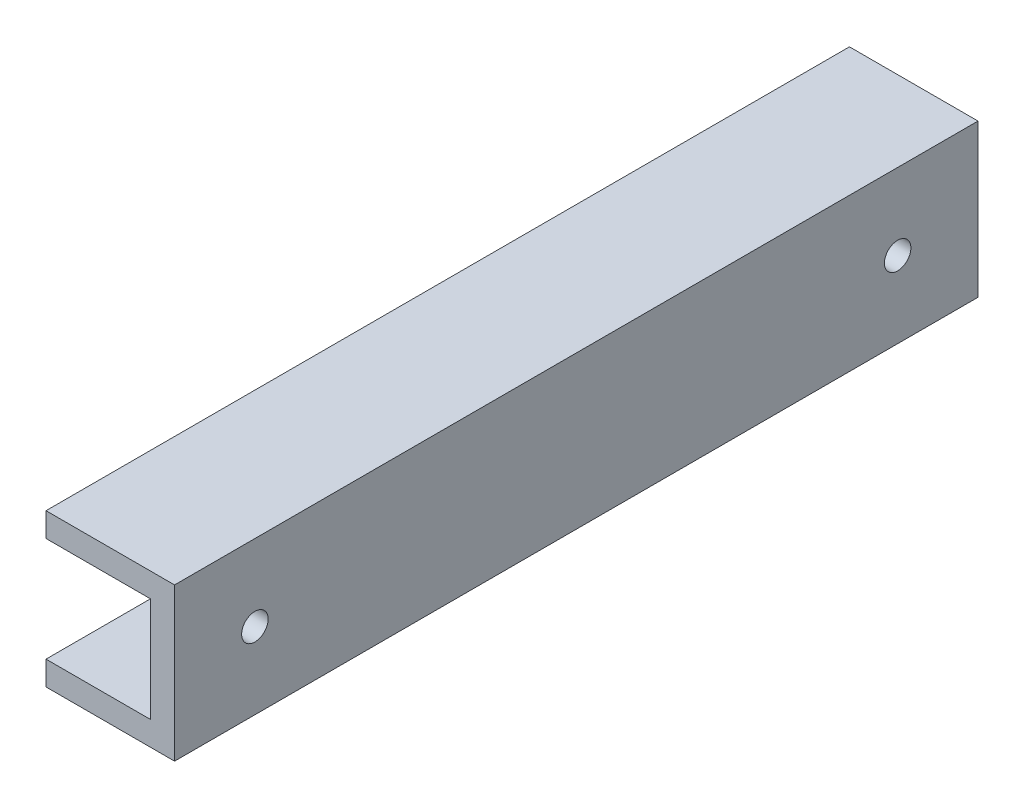
SolidWorks part; units mm, degrees
ref_plane "前视基准面" through (0, 0, 0) normal (0, 0, 1) x (1, 0, 0)
ref_plane "上视基准面" through (0, 0, 0) normal (0, 1, 0) x (1, 0, 0)
ref_plane "右视基准面" through (0, 0, 0) normal (1, 0, 0) x (0, 0, -1)
sketch "草图1" plane through (0, 0, 0) normal (0, 0, 1) x (1, 0, 0)
  line L1 (0, 0) -> (13, 0)
  line L2 (0, 0) -> (0, 13)
  line L3 (0, 13) -> (13, 13)
  line L4 (13, 0) -> (13, 13)
  dimension "D1" = 13
  dimension "D2" = 13
extrude "拉伸-薄壁1" add sketch "草图1" along normal blind 100 thin
sketch "草图2" plane through (-3, 0, 0) normal (-1, 0, 0) x (0, 0, 1)
  line L0 (0, 16) -> (0, -3) construction
  line L1 (100, 16) -> (100, -3) construction
  circle A0 centre (10, 6.5) radius 1.65
  circle A1 centre (90, 6.5) radius 1.65
  dimension "D1" = 3.3
  dimension "D2" = 3.3
  dimension "D3" = 10
  dimension "D4" = 10
extrude "切除-拉伸1" cut sketch "草图2" against normal blind 30
sketch "草图3" plane through (-3, 0, 0) normal (-1, 0, 0) x (0, 0, 1)
  line L1 (-5.2954, 23.3125) -> (111.6198, 23.3125)
  line L2 (-5.2954, 23.3125) -> (-5.2954, -22.907)
  line L3 (-5.2954, -22.907) -> (111.6198, -22.907)
  line L4 (111.6198, 23.3125) -> (111.6198, -22.907)
extrude "切除-拉伸2" cut sketch "草图3" against normal blind 3
sketch "草图4" plane through (13, 0, 0) normal (-1, 0, 0) x (0, 0, 1)
  line L0 (100, 13) -> (0, 13) construction
  line L1 (23, 13) -> (28, 13)
  line L2 (23, 13) -> (23, 0)
  line L3 (23, 0) -> (28, 0)
  line L4 (28, 13) -> (28, 0)
  line L5 (100, 0) -> (0, 0) construction
  line L6 (100, 13) -> (0, 13) construction
  line L7 (72, 13) -> (77, 13)
  line L8 (72, 13) -> (72, 0)
  line L9 (72, 0) -> (77, 0)
  line L10 (77, 13) -> (77, 0)
  line L11 (100, 0) -> (0, 0) construction
  line L12 (100, 0) -> (100, 13) construction
  line L13 (0, 0) -> (0, 13) construction
  dimension "D1" = 23
  dimension "D2" = 23
  dimension "D3" = 5
  dimension "D4" = 5
extrude "凸台-拉伸1" add sketch "草图4" along normal blind 10
sketch "草图5" plane through (13, 0, 0) normal (-1, 0, 0) x (0, 0, 1)
  line L0 (28, 0) -> (28, 13) construction
  line L1 (28, 9) -> (72, 9)
  line L2 (28, 9) -> (28, 4)
  line L3 (28, 4) -> (72, 4)
  line L4 (72, 9) -> (72, 4)
  line L5 (72, 13) -> (72, 0) construction
  line L6 (72, 0) -> (28, 0) construction
  dimension "D1" = 5
  dimension "D2" = 4
extrude "凸台-拉伸2" add sketch "草图5" along normal blind 10
sketch "草图6" plane through (13, 0, 0) normal (-1, 0, 0) x (0, 0, 1)
  line L1 (23, 13) -> (77, 13)
  line L2 (23, 13) -> (23, 0)
  line L3 (23, 0) -> (77, 0)
  line L4 (77, 13) -> (77, 0)
extrude "凸台-拉伸3" add sketch "草图6" along normal blind 10
sketch "草图7" plane through (3, 0, 0) normal (-1, 0, 0) x (0, 0, 1)
  line L0 (23, 13) -> (23, 0) construction
  line L1 (23, 9) -> (77, 9)
  line L2 (23, 9) -> (23, 4)
  line L3 (23, 4) -> (77, 4)
  line L4 (77, 9) -> (77, 4)
  line L5 (77, 0) -> (77, 13) construction
  line L6 (100, 13) -> (0, 13) construction
  dimension "D1" = 5
  dimension "D2" = 4
extrude "凸台-拉伸4" [suppressed] add sketch "草图7" along normal blind 3
sketch "草图8" plane through (3, 0, 0) normal (-1, 0, 0) x (0, 0, 1)
  line L0 (23, 13) -> (23, 0) construction
  line L1 (23, 9) -> (77, 9)
  line L2 (23, 9) -> (23, 4)
  line L3 (23, 4) -> (77, 4)
  line L4 (77, 9) -> (77, 4)
  line L5 (77, 0) -> (77, 13) construction
  line L6 (100, 13) -> (0, 13) construction
  dimension "D1" = 5
  dimension "D2" = 4
extrude "切除-拉伸3" cut sketch "草图8" against normal blind 8
chamfer "倒角1" distance 3 angle 45 2 edges at (11, 6.5, 77) (11, 6.5, 23)
chamfer "倒角2" distance 4 angle 45 2 edges at (13, 2, 77) (13, 11, 23)
sketch "草图9" plane through (11, 0, 0) normal (-1, 0, 0) x (0, 0, 1)
  text T0 "L3"
extrude "切除-拉伸4" cut sketch "草图9" against normal blind 0.3
